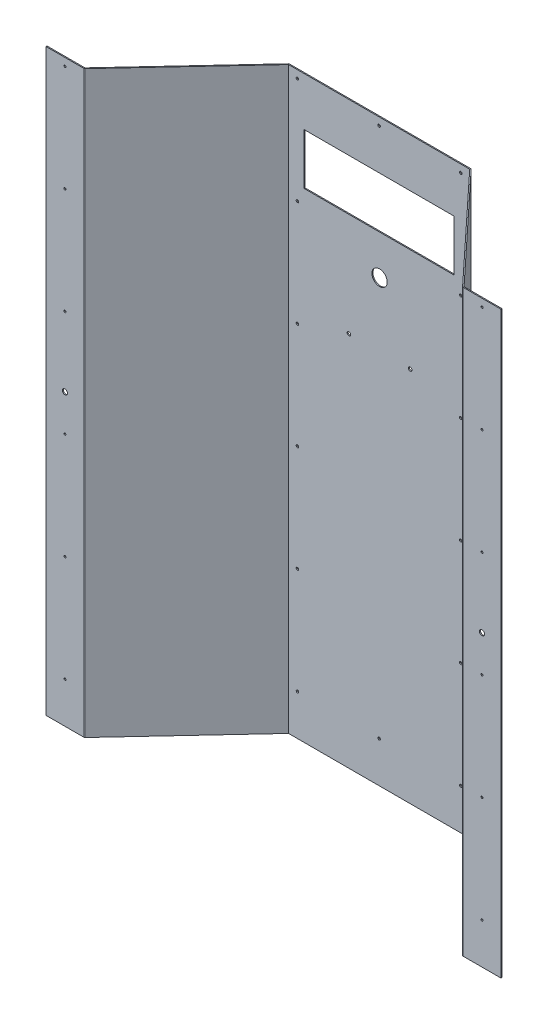
SolidWorks part; units mm, degrees
note: The reader was unsure of these and kept them because the rebuilt part matched: flange length of "Ребро-кромка1", "Ребро-кромка2".
ref_plane "Спереди" through (0, 0, 0) normal (0, 0, 1) x (1, 0, 0)
ref_plane "Сверху" through (0, 0, 0) normal (0, 1, 0) x (1, 0, 0)
ref_plane "Справа" through (0, 0, 0) normal (1, 0, 0) x (0, 0, -1)
sketch "Эскиз1" plane through (0, 0, 0) normal (0, 0, 1) x (1, 0, 0)
  line L1 (0, 0) -> (355, 0)
  line L2 (0, 0) -> (0, 1135)
  line L3 (0, 1135) -> (355, 1135)
  line L4 (355, 0) -> (355, 1135)
  dimension "D1" = 1135
  dimension "D2" = 355
base flange "Базовая кромка2" sketch "Эскиз1" thickness 2 reverse thickness direction no parameters "D1"=0.7366
sketch "Эскиз17" plane through (0, 0, 0) normal (0, 1, 0) x (1, 0, 0)
  line L0 (16.2703, 72.7806) -> (16.2703, -117.2194) construction
  line L1 (16.2703, -117.2194) -> (226.2703, -117.2194) construction
  line L2 (226.2703, -117.2194) -> (16.2703, 72.7806) construction
  dimension "D1" = 190
  dimension "D2" = 210
edge flange "Ребро-кромка1" sketch "Эскиз22" flange profiles "Эскиз22", "Эскиз23" flange angle 133 flange length 283 flange position material outside bend radius 0.7366 thickness 2 relief rectangular parameters "D6"=10, "D8"=1
sketch "Эскиз22" plane through (0, 0, 0) normal (-0.7314, 0, -0.682) x (0, -1, 0)
  line L2 (-1135, 0) -> (-1135, 282.1304)
  line L3 (-1135, 282.1304) -> (0, 282.1304)
  line L4 (0, 282.1304) -> (0, 0)
  line L5 (-1135, 0) -> (0, 0) construction
  line L6 (-1135, 0) -> (0, 0)
sketch "Эскиз23" plane through (355, 0, 0) normal (0.7314, 0, -0.682) x (0, 1, 0)
  line L0 (0, 0) -> (1135, 0) construction
  line L1 (0, 0) -> (1135, 0)
  line L2 (0, 0) -> (0, 282.1304)
  line L3 (0, 282.1304) -> (1135, 282.1304)
  line L4 (1135, 282.1304) -> (1135, 0)
bend "EdgeBend1" bend radius 0.7366 bend angle 47 parameters "D5"=1
bend "EdgeBend2" bend radius 0.7366 bend angle 47 parameters "D5"=2
edge flange "Ребро-кромка2" sketch "Эскиз28" flange profiles "Эскиз28", "Эскиз29" flange angle 133 flange length 75 flange position material outside bend radius 0.7366 thickness 2 relief rectangular parameters "D6"=10, "D8"=1
sketch "Эскиз28" plane through (548.8752, 0, 204.9731) normal (0, 0, 1) x (0, -1, 0)
  line L2 (-1135, 0) -> (-1135, 74.1304)
  line L3 (-1135, 74.1304) -> (0, 74.1304)
  line L4 (0, 74.1304) -> (0, 0)
  line L5 (-1135, 0) -> (0, 0) construction
  line L6 (-1135, 0) -> (0, 0)
sketch "Эскиз29" plane through (-193.8752, 0, 204.9731) normal (0, 0, 1) x (0, 1, 0)
  line L0 (0, 0) -> (1135, 0) construction
  line L1 (0, 0) -> (1135, 0)
  line L2 (0, 0) -> (0, 74.1304)
  line L3 (0, 74.1304) -> (1135, 74.1304)
  line L4 (1135, 74.1304) -> (1135, 0)
bend "EdgeBend3" bend radius 0.7366 bend angle 47 parameters "D5"=3
bend "EdgeBend4" bend radius 0.7366 bend angle 47 parameters "D5"=4
sketch "Эскиз30" plane through (0, 0, -2) normal (0, 0, -1) x (-1, 0, 0)
  line L0 (-354.6797, 1135) -> (-354.6797, 0) construction
  line L1 (-324.6797, 1040) -> (-30.3203, 1040)
  line L2 (-324.6797, 1040) -> (-324.6797, 940)
  line L3 (-324.6797, 940) -> (-30.3203, 940)
  line L4 (-30.3203, 1040) -> (-30.3203, 940)
  line L5 (-0.3203, 0) -> (-0.3203, 1135) construction
  line L7 (-0.3203, 0) -> (-354.6797, 0) construction
  dimension "D1" = 30
  dimension "D2" = 30
  dimension "D3" = 940
  dimension "D4" = 100
extrude "Вырез-Вытянуть1" cut sketch "Эскиз30" against normal up to next normal cut yes
sketch "Эскиз31" plane through (0, 0, 204.9731) normal (0, 0, -1) x (-1, 0, 0)
  line L0 (-585.9403, 1135) -> (-586.1005, 0) construction
  line L1 (-548.8752, 1135) -> (-623.0055, 1135) construction
  line L2 (-549.1954, 0) -> (-623.0055, 0) construction
  line L3 (-586.1005, 0) -> (231.1005, 1135) construction
  line L4 (194.1954, 1135) -> (268.0055, 1135) construction
  line L5 (231.1005, 1135) -> (231.1005, 0) construction
  line L6 (268.0055, 0) -> (194.1954, 0) construction
  circle A0 centre (-586.0204, 567.5) radius 5
  circle A1 centre (231.1005, 567.5) radius 5
  dimension "D1" = 10
extrude "Вырез-Вытянуть2" cut sketch "Эскиз31" against normal up to next normal cut yes
sketch "Эскиз32" plane through (0, 0, 0) normal (0, 0, 1) x (1, 0, 0)
  circle A0 centre (118.3203, 737.5) radius 3.5
  circle A1 centre (238.3203, 737.5) radius 3.5
  dimension "D1" = 7
extrude "Вырез-Вытянуть3" cut sketch "Эскиз32" against normal up to next normal cut yes
sketch "Эскиз33" plane through (0, 0, 0) normal (0, 0, 1) x (1, 0, 0)
  circle A0 centre (17.5055, 1120) radius 2.5
  circle A1 centre (177.5055, 1120) radius 2.5
  circle A2 centre (337.5055, 1120) radius 2.5
  circle A3 centre (17.5055, 912) radius 2.5
  circle A4 centre (17.5055, 704) radius 2.5
  circle A5 centre (17.5055, 496) radius 2.5
  circle A6 centre (17.5055, 288) radius 2.5
  circle A7 centre (17.5055, 80) radius 2.5
  circle A8 centre (177.5055, 80) radius 2.5
  circle A9 centre (337.5055, 80) radius 2.5
  circle A10 centre (337.5055, 496) radius 2.5
  circle A11 centre (337.5055, 288) radius 2.5
  circle A12 centre (337.5055, 704) radius 2.5
  circle A13 centre (337.5055, 912) radius 2.5
  dimension "D1" = 5
extrude "Вырез-Вытянуть4" cut sketch "Эскиз33" against normal up to next normal cut yes
sketch "Эскиз34" plane through (0, 0, -2) normal (0, 0, -1) x (-1, 0, 0)
  line L0 (-238.3203, 737.5) -> (-118.3203, 737.5) construction
  line L1 (-178.3203, 737.5) -> (-178.3203, 862.5) construction
  circle A0 centre (-178.3203, 862.5) radius 15
  dimension "D2" = 30
  dimension "D1" = 125
extrude "Вырез-Вытянуть5" cut sketch "Эскиз34" against normal through all normal cut yes
sketch "Эскиз35" plane through (0, 0, 204.9731) normal (0, 0, -1) x (-1, 0, 0)
  line L0 (-586.1005, 1135) -> (-586.1005, 0) construction
  line L1 (-623.0055, 1135) -> (-549.1954, 1135) construction
  line L2 (-549.1954, 0) -> (-623.0055, 0) construction
  line L3 (-586.1005, 0) -> (231.1005, 1135) construction
  line L4 (194.1954, 1135) -> (268.0055, 1135) construction
  line L5 (231.1005, 1135) -> (231.1005, 0) construction
  line L6 (268.0055, 0) -> (194.1954, 0) construction
  line L7 (-586.1005, 1120) -> (231.1005, 1120) construction
  line L8 (231.1005, 1120) -> (-586.1005, 912) construction
  line L9 (-586.1005, 912) -> (231.1005, 912) construction
  line L10 (231.1005, 912) -> (-586.1005, 704) construction
  line L11 (-586.1005, 704) -> (231.1005, 704) construction
  line L12 (231.1005, 704) -> (-586.1005, 496) construction
  line L13 (-586.1005, 496) -> (231.1005, 496) construction
  line L14 (231.1005, 496) -> (-586.1005, 288) construction
  line L15 (-586.1005, 288) -> (231.1005, 288) construction
  line L16 (231.1005, 288) -> (-586.1005, 80) construction
  line L17 (-586.1005, 80) -> (231.1005, 80) construction
  circle A0 centre (-586.1005, 1120) radius 2
  circle A1 centre (-586.1005, 912) radius 2
  circle A2 centre (-586.1005, 704) radius 2
  circle A3 centre (-586.1005, 496) radius 2
  circle A4 centre (-586.1005, 288) radius 2
  circle A5 centre (-586.1005, 80) radius 2
  circle A6 centre (231.1005, 80) radius 2
  circle A7 centre (231.1005, 288) radius 2
  circle A8 centre (231.1005, 496) radius 2
  circle A9 centre (231.1005, 704) radius 2
  circle A10 centre (231.1005, 912) radius 2
  circle A11 centre (231.1005, 1120) radius 2
  dimension "D4" = 4
  dimension "D1" = 15
  dimension "D2" = 208
  dimension "D3" = 208
extrude "Вырез-Вытянуть6" cut sketch "Эскиз35" against normal through all normal cut yes
sketch "Сгиб-Линии3" plane through (0, 0, 0) normal (0, 1, 0) x (1, 0, 0)
sketch "Граничная рамка3" plane through (0, 0, 0) normal (0, 1, 0) x (1, 0, 0)
sheet metal parameters "Листовой металл4" thickness 2 parameters "D1"=0.7366
flat pattern "Развертка4" [suppressed]
sketch "Сгиб-Линии4" plane through (0, 0, 0) normal (0, 1, 0) x (1, 0, 0)
sketch "Граничная рамка4" [suppressed] plane through (0, 0, 0) normal (0, 1, 0) x (1, 0, 0)
sheet metal parameters "Листовой металл5" thickness 2 parameters "D1"=0.7366
flat pattern "Развертка4" [suppressed]
sketch "Сгиб-Линии4" plane through (0, 0, 0) normal (0, 1, 0) x (1, 0, 0)
sketch "Граничная рамка4" [suppressed] plane through (0, 0, 0) normal (0, 1, 0) x (1, 0, 0)
bend of the flat pattern "Плоское состояние-<EdgeBend1>1"
bend of the flat pattern "Плоское состояние-<EdgeBend2>1"
sheet metal parameters "Листовой металл6" thickness 2 parameters "D1"=0.7366
flat pattern "Развертка4" [suppressed]
sketch "Сгиб-Линии4" plane through (0, 0, 0) normal (0, 1, 0) x (1, 0, 0)
sketch "Граничная рамка4" [suppressed] plane through (0, 0, 0) normal (0, 1, 0) x (1, 0, 0)
bend of the flat pattern "Плоское состояние-<EdgeBend1>1"
bend of the flat pattern "Плоское состояние-<EdgeBend2>1"
bend of the flat pattern "Плоское состояние-<EdgeBend3>1"
bend of the flat pattern "Плоское состояние-<EdgeBend4>1"
sheet metal parameters "Листовой металл7" thickness 2 parameters "D1"=0.7366
flat pattern "Развертка4" [suppressed]
sketch "Сгиб-Линии4" plane through (0, 0, 0) normal (0, 1, 0) x (1, 0, 0)
sketch "Граничная рамка4" [suppressed] plane through (0, 0, 0) normal (0, 1, 0) x (1, 0, 0)
bend of the flat pattern "Плоское состояние-<EdgeBend1>1"
bend of the flat pattern "Плоское состояние-<EdgeBend2>1"
bend of the flat pattern "Плоское состояние-<EdgeBend3>1"
bend of the flat pattern "Плоское состояние-<EdgeBend4>1"
sheet metal parameters "Листовой металл8" thickness 2 parameters "D1"=0.7366
flat pattern "Развертка4" [suppressed]
sketch "Сгиб-Линии4" plane through (0, 0, 0) normal (0, 1, 0) x (1, 0, 0)
sketch "Граничная рамка4" [suppressed] plane through (0, 0, 0) normal (0, 1, 0) x (1, 0, 0)
bend of the flat pattern "Плоское состояние-<EdgeBend1>1"
bend of the flat pattern "Плоское состояние-<EdgeBend2>1"
bend of the flat pattern "Плоское состояние-<EdgeBend3>1"
bend of the flat pattern "Плоское состояние-<EdgeBend4>1"
sheet metal parameters "Листовой металл9" thickness 2 parameters "D1"=0.7366
flat pattern "Развертка4" [suppressed]
sketch "Сгиб-Линии4" plane through (0, 0, 0) normal (0, 1, 0) x (1, 0, 0)
sketch "Граничная рамка4" [suppressed] plane through (0, 0, 0) normal (0, 1, 0) x (1, 0, 0)
bend of the flat pattern "Плоское состояние-<EdgeBend1>1"
bend of the flat pattern "Плоское состояние-<EdgeBend2>1"
bend of the flat pattern "Плоское состояние-<EdgeBend3>1"
bend of the flat pattern "Плоское состояние-<EdgeBend4>1"
sheet metal parameters "Листовой металл10" thickness 2 parameters "D1"=0.7366
flat pattern "Развертка4" [suppressed]
sketch "Сгиб-Линии4" plane through (0, 0, 0) normal (0, 1, 0) x (1, 0, 0)
sketch "Граничная рамка4" [suppressed] plane through (0, 0, 0) normal (0, 1, 0) x (1, 0, 0)
bend of the flat pattern "Плоское состояние-<EdgeBend1>1"
bend of the flat pattern "Плоское состояние-<EdgeBend2>1"
bend of the flat pattern "Плоское состояние-<EdgeBend3>1"
bend of the flat pattern "Плоское состояние-<EdgeBend4>1"
sheet metal parameters "Листовой металл11" thickness 2 parameters "D1"=0.7366
flat pattern "Развертка4" [suppressed]
sketch "Сгиб-Линии4" plane through (0, 0, 0) normal (0, 1, 0) x (1, 0, 0)
sketch "Граничная рамка4" [suppressed] plane through (0, 0, 0) normal (0, 1, 0) x (1, 0, 0)
bend of the flat pattern "Плоское состояние-<EdgeBend1>1"
bend of the flat pattern "Плоское состояние-<EdgeBend2>1"
bend of the flat pattern "Плоское состояние-<EdgeBend3>1"
bend of the flat pattern "Плоское состояние-<EdgeBend4>1"
sheet metal parameters "Листовой металл12" thickness 2 parameters "D1"=0.7366
flat pattern "Развертка4" [suppressed]
sketch "Сгиб-Линии4" plane through (0, 0, 0) normal (0, 1, 0) x (1, 0, 0)
sketch "Граничная рамка4" [suppressed] plane through (0, 0, 0) normal (0, 1, 0) x (1, 0, 0)
bend of the flat pattern "Плоское состояние-<EdgeBend1>1"
bend of the flat pattern "Плоское состояние-<EdgeBend2>1"
bend of the flat pattern "Плоское состояние-<EdgeBend3>1"
bend of the flat pattern "Плоское состояние-<EdgeBend4>1"
